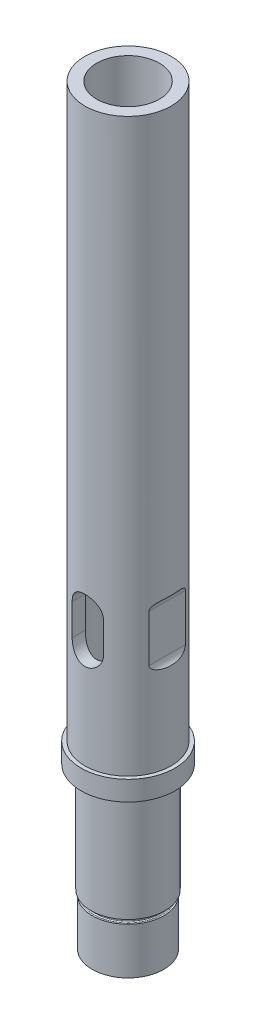
SolidWorks part; units mm, degrees
material "AISI 304"
ref_plane "Front Plane" through (0, 0, 0) normal (0, 0, 1) x (1, 0, 0)
ref_plane "Top Plane" through (0, 0, 0) normal (0, 1, 0) x (1, 0, 0)
ref_plane "Right Plane" through (0, 0, 0) normal (1, 0, 0) x (0, 0, -1)
sketch "Sketch1" plane through (0, 0, 0) normal (0, 1, 0) x (1, 0, 0)
  circle A0 centre (0, 0) radius 9.525
  circle A1 centre (0, 0) radius 22.5
  dimension "D1" = 45
  dimension "D2" = 19.05
extrude "Boss-Extrude1" add sketch "Sketch1" along normal blind 95
sketch "Sketch2" plane through (0, 0, 0) normal (0, -1, 0) x (1, 0, 0)
  circle A0 centre (0, 0) radius 15
  dimension "D1" = 30
extrude "Cut-Extrude1" cut sketch "Sketch2" against normal blind 50 flip side to cut
sketch "Sketch4" plane through (0, 95, 0) normal (0, 1, 0) x (1, 0, 0)
  circle A0 centre (0, 0) radius 17.5
  dimension "D1" = 35
extrude "Cut-Extrude2" cut sketch "Sketch4" against normal blind 37 flip side to cut
sketch "Sketch11" plane through (0, 0, 0) normal (0, -1, 0) x (1, 0, 0)
  circle A0 centre (0, 0) radius 14.513
  dimension "D1" = 29.026
extrude "Cut-Extrude3" cut sketch "Sketch11" against normal blind 5.88 flip side to cut
sketch "Sketch12" plane through (0, 95, 0) normal (0, 1, 0) x (1, 0, 0)
  circle A0 centre (0, 0) radius 9.525 construction
  circle A1 centre (0, 0) radius 17.5
  circle A2 centre (0, 0) radius 17.5
  circle A3 centre (0, 0) radius 9.525
  dimension "D1" = 0
extrude "Boss-Extrude2" add sketch "Sketch12" along normal blind 203.2
sketch "Sketch13" plane through (0, 0, 0) normal (0, -1, 0) x (1, 0, 0)
  circle A0 centre (0, 0) radius 9.525
  circle A1 centre (0, 0) radius 15
  circle A2 centre (0, 0) radius 14.513
  circle A3 centre (0, 0) radius 14.513 construction
  circle A4 centre (0, 0) radius 9.525 construction
  circle M2 centre (0, 0) radius 14.513
  dimension "D2" = 30
  dimension "D3" = 0
extrude "Boss-Extrude3" add sketch "Sketch13" along normal blind 15 contours A1 M2 region at (-14.1025, 0, 0)
sketch "Sketch15" plane through (0, 50, 0) normal (0, -1, 0) x (1, 0, 0)
  circle A0 centre (0, 0) radius 19.05
  dimension "D1" = 38.1
extrude "Cut-Extrude5" cut sketch "Sketch15" against normal through all flip side to cut
sketch "Sketch16" plane through (0, 5.88, 0) normal (0, -1, 0) x (1, 0, 0)
  circle A0 centre (0, 0) radius 13.5
  dimension "D1" = 27
extrude "Cut-Extrude6" cut sketch "Sketch16" along normal blind 2 flip side to cut
fillet "Fillet2" radius 0.3969 2 edges at (0, 5.88, -13.5) (0, 3.88, -13.5)
sketch "Sketch17" plane through (0, 298.2, 0) normal (0, 1, 0) x (1, 0, 0)
  circle A1 centre (0, 0) radius 17.5
  circle A2 centre (0, 0) radius 17.5
  dimension "D1" = 0
extrude "Cut-Extrude7" cut sketch "Sketch17" against normal offset from surface (8.4 mm away) 304.8 up to face at (0, -15, -14.513)
sketch "Sketch20" plane through (0, 0, 0) normal (0, 0, 1) x (1, 0, 0)
  line L1 (-19.05, 118.325) -> (-15.875, 118.325)
  line L2 (-19.05, 118.325) -> (-19.05, 92.925)
  line L3 (-19.05, 92.925) -> (-15.875, 92.925)
  line L4 (-15.875, 118.325) -> (-15.875, 92.925)
  line L5 (15.875, 118.325) -> (19.05, 118.325)
  line L6 (15.875, 118.325) -> (15.875, 92.925)
  line L7 (15.875, 92.925) -> (19.05, 92.925)
  line L8 (19.05, 118.325) -> (19.05, 92.925)
  line L9 (0, 289.8) -> (0, -15) construction
  line L10 (19.05, 58) -> (-19.05, 58) construction
  line L11 (-19.05, 58) -> (-19.05, 50) construction
  line L12 (19.05, 50) -> (19.05, 58) construction
  dimension "D2" = 15.875
  dimension "D1" = 15.875
  dimension "D3" = 34.925
  dimension "D4" = 25.4
extrude "Cut-Extrude8" cut sketch "Sketch20" against normal through all both and the other way through all
fillet "Fillet3" radius 3.175 4 edges at (-15.875, 92.925, 0) (-15.875, 118.325, 0) (15.875, 92.925, 0) (15.875, 118.325, 0)
sketch "Sketch21" plane through (0, 0, 0) normal (0, 0, 1) x (1, 0, 0)
  line L0 (-15.875, 105.625) -> (15.875, 105.625) construction
  line L1 (-15.875, 96.1) -> (-15.875, 115.15) construction
  line L2 (15.875, 115.15) -> (15.875, 96.1) construction
  line L3 (0, 289.8) -> (0, -15) construction
  line L4 (0, 99.275) -> (0, 111.975) construction
  line L5 (-6.35, 99.275) -> (-6.35, 111.975)
  line L6 (6.35, 99.275) -> (6.35, 111.975)
  arc A1 (-6.35, 99.275) -> (6.35, 99.275) centre (0, 99.275) ccw
  arc A2 (6.35, 111.975) -> (-6.35, 111.975) centre (0, 111.975) ccw
  point P11 (0, 105.625)
  dimension "D1" = 6.35
  dimension "D3" = 6.35
  dimension "D2" = 12.7
  dimension "D4" = 12.7
extrude "Cut-Extrude9" cut sketch "Sketch21" along normal up to surface (16.3073 mm away) up to face at (-16.6875, 105.625, 0)
sketch "Sketch22" plane through (0, 289.8, 0) normal (0, 1, 0) x (1, 0, 0)
  circle A0 centre (0, 0) radius 12.7
  dimension "D1" = 25.4
extrude "Cut-Extrude10" cut sketch "Sketch22" against normal up to surface (304.8 mm away) up to face at (0, -15, -14.513)
equation "\"D1@Sketch20\"=\"D2@Sketch20\""
